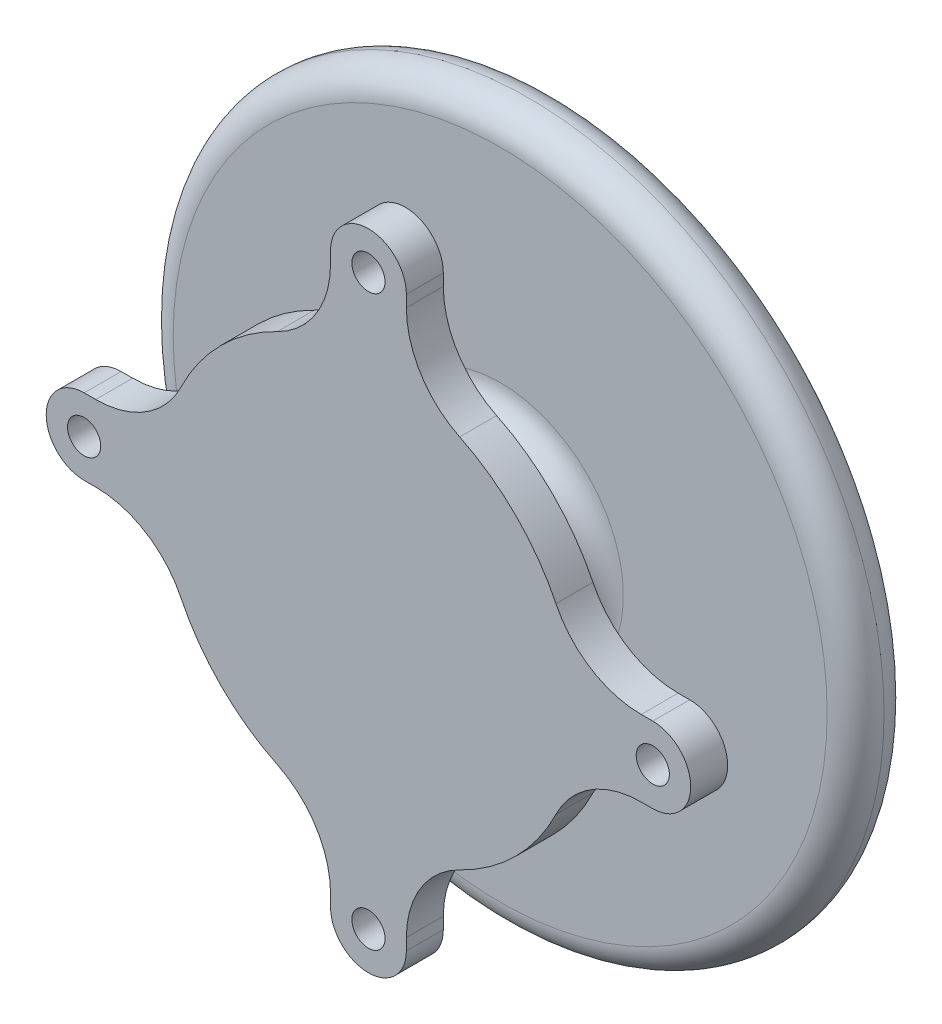
SolidWorks part; units mm, degrees
ref_plane "Front Plane" through (0, 0, 0) normal (0, 0, 1) x (1, 0, 0)
ref_plane "Top Plane" through (0, 0, 0) normal (0, 1, 0) x (1, 0, 0)
ref_plane "Right Plane" through (0, 0, 0) normal (1, 0, 0) x (0, 0, -1)
sketch "Sketch1" plane through (0, 0, 0) normal (0, 0, 1) x (1, 0, 0)
  circle A0 centre (0, 0) radius 25
  dimension "D1" = 50
ref_plane "Plane1" through (0, 0, 20) normal (0, 0, 1) x (1, 0, 0)
sketch "Sketch2" plane through (0, 0, 20) normal (0, 0, 1) x (1, 0, 0)
  circle A0 centre (0, 0) radius 15
  dimension "D1" = 30
loft "Loft1" add profiles "Sketch2", "Sketch1" connector at (-14.1852, 4.8766, 20) connector at (-23.533, 8.4378, 0)
sketch "Sketch3" plane through (0, 0, 20) normal (0, 0, 1) x (1, 0, 0)
  circle A0 centre (0, 0) radius 15
  circle A1 centre (0, 0) radius 15 construction
extrude "Boss-Extrude1" add sketch "Sketch3" along normal blind 5
fillet "Fillet1" radius 10 1 edges at (15, 0, 20)
sketch "Sketch4" plane through (0, 0, 0) normal (0, 0, -1) x (-1, 0, 0)
  line L0 (0, 20) -> (0, -20) construction
  line L1 (-20, 0) -> (20, 0) construction
  circle A0 centre (0, 0) radius 20 construction
  circle A1 centre (0, 20) radius 1.75
  circle A2 centre (-20, 0) radius 1.75
  circle A3 centre (0, -20) radius 1.75
  circle A4 centre (20, 0) radius 1.75
  dimension "D1" = 40
  dimension "D2" = 3.5
  dimension "D3" = 3.5
  dimension "D4" = 3.5
  dimension "D5" = 3.5
extrude "Cut-Extrude1" cut sketch "Sketch4" against normal blind 130
ref_plane "Plane2" through (0, 0, 3) normal (0, 0, -1) x (-1, 0, 0)
sketch "Sketch5" plane through (0, 0, 3) normal (0, 0, -1) x (-1, 0, 0)
  circle A0 centre (0, 20) radius 4
  circle A1 centre (20, 0) radius 4
  circle A3 centre (-20, 0) radius 4
  circle A5 centre (0, -20) radius 4
  dimension "D1" = 8
  dimension "D2" = 8
  dimension "D3" = 8
  dimension "D4" = 8
extrude "Cut-Extrude2" cut sketch "Sketch5" against normal blind 130
sketch "Sketch6" plane through (0, 0, 25) normal (0, 0, 1) x (1, 0, 0)
  circle A0 centre (0, 0) radius 22
  dimension "D1" = 44
extrude "Boss-Extrude2" add sketch "Sketch6" along normal blind 4
sketch "Sketch7" plane through (0, 0, 29) normal (0, 0, 1) x (1, 0, 0)
  circle A0 centre (0, 0) radius 17
  circle A1 centre (0, 0) radius 22 construction
  dimension "D1" = 5
extrude "Boss-Extrude3" add sketch "Sketch7" along normal blind 20
sketch "Sketch8" [suppressed] plane through (0, 0, 0) normal (0, 1, 0) x (1, 0, 0)
  line L0 (0, -48) -> (0, -27)
  line L1 (-17, -48) -> (17, -48) construction
  line L3 (17, -48) -> (17, -28) construction
  line L4 (3, -24) -> (45.4819, -24)
  arc A0 (0, -27) -> (3, -24) centre (3, -27) cw
  point P9 (0, -24)
  dimension "D2" = 3
  dimension "D1" = 24
  dimension "D3" = 17
ref_plane "Plane5" through (14, 0, 0) normal (1, 0, 0) x (0, 0, -1)
sketch "Sketch14" [suppressed] plane through (14, 0, 0) normal (1, 0, 0) x (0, 0, -1)
  line L0 (-28, 20) -> (-28, -20) construction
  circle A0 centre (-24, 0) radius 4
  dimension "D1" = 8
sketch "Sketch9" [suppressed] plane through (0, 0, 48) normal (0, 0, 1) x (1, 0, 0)
  circle A0 centre (0, 0) radius 2.1
  dimension "D1" = 4.2
ref_plane "Plane4" through (14, 0, 0) normal (1, 0, 0) x (0, 0, -1)
sketch "Sketch10" plane through (0, 0, 49) normal (0, 0, 1) x (1, 0, 0)
  circle A0 centre (0, 0) radius 10
  circle A1 centre (0, 0) radius 17 construction
  dimension "D1" = 7
sketch "Sketch13" [suppressed] plane through (0, 0, 0) normal (0, 1, 0) x (1, 0, 0)
  line L0 (17, -28) -> (17, -48) construction
  line L1 (-20, -28) -> (20, -28) construction
  line L2 (17, -31.3668) -> (17, -44.6332)
  line L3 (0, -28) -> (0, -48) construction
  line L4 (-17, -28) -> (17, -28) construction
  line L5 (-17, -48) -> (17, -48) construction
  arc A0 (17, -31.3668) -> (17, -44.6332) centre (38.5, -38) ccw
  dimension "D1" = 45
  dimension "D2" = 21.5
  dimension "D3" = 10
ref_plane "Plane14" through (0, 0, 39) normal (0, 0, 1) x (1, 0, 0)
sketch "Sketch15" plane through (0, 0, 0) normal (0, 1, 0) x (1, 0, 0)
  line L0 (-17, -29) -> (-17, -49) construction
  line L1 (-21.4316, -33) -> (-13, -33)
  line L2 (-21.4316, -33) -> (-21.4316, -37)
  line L3 (-21.4316, -37) -> (-13, -37)
  line L4 (-13, -33) -> (-13, -37)
  line L5 (-21.5787, -41) -> (-13, -41)
  line L6 (-21.5787, -41) -> (-21.5787, -45)
  line L7 (-21.5787, -45) -> (-13, -45)
  line L8 (-13, -41) -> (-13, -45)
  line L9 (-17, -29) -> (17, -29) construction
  line L10 (0, -29) -> (0, -49) construction
  line L11 (-17, -49) -> (17, -49) construction
  dimension "D1" = 4
  dimension "D2" = 4
  dimension "D3" = 4
  dimension "D4" = 4
  dimension "D5" = 4
  dimension "D6" = 4
revolve "Cut-Revolve1" cut sketch "Sketch15" angle 360 about L10
sketch "Sketch18" plane through (0, 0, 0) normal (0, 0, -1) x (-1, 0, 0)
  circle A0 centre (0, 0) radius 12.5
  dimension "D1" = 25
extrude "Cut-Extrude5" cut sketch "Sketch18" against normal blind 20
sketch "Sketch19" plane through (0, 0, 25) normal (0, 0, -1) x (-1, 0, 0)
  circle A0 centre (0, 0) radius 47.9872
extrude "Cut-Extrude6" cut sketch "Sketch19" along normal through all
sketch "Sketch20" plane through (0, 0, 25) normal (0, 0, -1) x (-1, 0, 0)
  line L0 (-4, 30) -> (-4, 21.6333)
  line L1 (4, 30) -> (4, 21.6333)
  arc A0 (4, 30) -> (-4, 30) centre (0, 30) ccw
  circle A1 centre (0, 30) radius 1.75
  arc A2 (4, 21.6333) -> (-4, 21.6333) centre (0, 0) ccw
  dimension "D1" = 8
  dimension "D2" = 3.5
  dimension "D3" = 44
  dimension "D4" = 30
extrude "Boss-Extrude5" add sketch "Sketch20" against normal blind 4
pattern_circular "CirPattern3" count 4 over 360 about axis through (0, 0, 25) along (0, 0, 1) of "Boss-Extrude5"
fillet "Fillet2" radius 10 8 edges at (21.6333, 4, 27) (21.6333, -4, 27) (4, -21.6333, 27) (-4, -21.6333, 27) (-21.6333, -4, 27) (-21.6333, 4, 27) (-4, 21.6333, 27) (4, 21.6333, 27)
sketch "Sketch21" plane through (0, 0, 29) normal (0, 0, 1) x (1, 0, 0)
  circle A0 centre (0, 0) radius 20
  circle A1 centre (0, 0) radius 17 construction
  circle A2 centre (0, 0) radius 26
  dimension "D1" = 3
  dimension "D2" = 6
chamfer "Chamfer1" distance 0.5 angle 45 5 edges at (-17, 0, 33) (-17, 0, 41) (17, 0, 37) (17, 0, 49) (17, 0, 45)
sketch "Sketch22" plane through (0, 0, 0) normal (0, 1, 0) x (1, 0, 0)
  line L0 (0, -49) -> (0, -60.7563) construction
  line L1 (7.5, -57) -> (-7.5, -57)
  line L2 (7.5, -57) -> (7.5, -49)
  line L3 (7.5, -49) -> (-7.5, -49)
  line L4 (-7.5, -57) -> (-7.5, -49)
  line L5 (-16.5, -49) -> (16.5, -49) construction
  dimension "D1" = 15
  dimension "D2" = 8
  dimension "D3" = 7.5
extrude "Boss-Extrude6" add sketch "Sketch22" along normal mid plane 15
sketch "Sketch23" plane through (0, 0, 0) normal (0, 1, 0) x (1, 0, 0)
  line L0 (0, -57) -> (0, -66) construction
  line L1 (-7.5, -57) -> (7.5, -57) construction
  line L2 (7.5, -57) -> (7.5, -49) construction
  line L3 (7.5, -53.0096) -> (7.5, -49)
  line L4 (-7.5, -49) -> (-7.5, -57) construction
  line L5 (-7.5, -49) -> (-7.5, -53.0096)
  line L6 (-7.5, -49) -> (7.5, -49)
  arc A0 (7.5, -53.0096) -> (-7.5, -53.0096) centre (0, -66) ccw
  dimension "D2" = 30
  dimension "D1" = 9
extrude "Cut-Extrude7" cut sketch "Sketch23" against normal mid plane 1.5
chamfer "Chamfer2" distance 3 angle 45 4 edges at (7.5, -7.5, 53) (7.5, 7.5, 53) (-7.5, -7.5, 53) (-7.5, 7.5, 53)
chamfer "Chamfer3" distance 0.5 angle 45 18 edges at (-6, -6, 57) (-7.5, 0, 57) (-6, 6, 57) (0, 7.5, 57) (6, 6, 57) (7.5, 0, 57) (6, -6, 57) (0, -7.5, 57) (7.5, 2.625, 49) (6, 6, 49) (0, 7.5, 49) (-6, 6, 49) (-7.5, 2.625, 49) (7.5, -2.625, 49) (6, -6, 49) (-7.5, -2.625, 49) (-6, -6, 49) (0, -7.5, 49)
sketch "Sketch24" plane through (0, 0, 29) normal (0, 0, 1) x (1, 0, 0)
  circle A0 centre (0, 0) radius 41.0173
  circle A1 centre (0, 0) radius 17 construction
  circle A2 centre (0, 0) radius 17
extrude "Cut-Extrude8" cut sketch "Sketch24" against normal blind 0.1
sketch "Sketch25" plane through (0, 0, 25) normal (0, 0, -1) x (-1, 0, 0)
  line L8 (4, 28.775) -> (4, 30)
  line L9 (-4, 30) -> (-4, 28.775)
  line L10 (-28.775, 4) -> (-30, 4)
  line L11 (-30, -4) -> (-28.775, -4)
  line L12 (-4, -28.775) -> (-4, -30)
  line L13 (4, -30) -> (4, -28.775)
  line L14 (28.775, -4) -> (30, -4)
  line L15 (30, 4) -> (28.775, 4)
  line L16 (4, 28.775) -> (4, 30)
  line L17 (-4, 30) -> (-4, 28.775)
  line L18 (-28.775, 4) -> (-30, 4)
  line L19 (-30, -4) -> (-28.775, -4)
  line L20 (-4, -28.775) -> (-4, -30)
  line L21 (4, -30) -> (4, -28.775)
  line L22 (28.775, -4) -> (30, -4)
  line L23 (30, 4) -> (28.775, 4)
  circle A0 centre (30, 0) radius 1.75 construction
  circle A1 centre (0, 30) radius 1.75 construction
  circle A2 centre (-30, 0) radius 1.75 construction
  circle A3 centre (0, -30) radius 1.75 construction
  circle A4 centre (30, 0) radius 1.75
  circle A5 centre (0, 30) radius 1.75
  circle A6 centre (-30, 0) radius 1.75
  circle A7 centre (0, -30) radius 1.75
  arc A16 (19.7828, 9.625) -> (9.625, 19.7828) centre (0, 0) ccw
  arc A17 (4, 28.775) -> (9.625, 19.7828) centre (14, 28.775) ccw
  arc A18 (4, 30) -> (-4, 30) centre (0, 30) ccw
  arc A19 (-9.625, 19.7828) -> (-4, 28.775) centre (-14, 28.775) ccw
  arc A20 (-9.625, 19.7828) -> (-19.7828, 9.625) centre (0, 0) ccw
  arc A21 (-28.775, 4) -> (-19.7828, 9.625) centre (-28.775, 14) ccw
  arc A22 (-30, 4) -> (-30, -4) centre (-30, 0) ccw
  arc A23 (-19.7828, -9.625) -> (-28.775, -4) centre (-28.775, -14) ccw
  arc A24 (-19.7828, -9.625) -> (-9.625, -19.7828) centre (0, 0) ccw
  arc A25 (-4, -28.775) -> (-9.625, -19.7828) centre (-14, -28.775) ccw
  arc A26 (-4, -30) -> (4, -30) centre (0, -30) ccw
  arc A27 (9.625, -19.7828) -> (4, -28.775) centre (14, -28.775) ccw
  arc A28 (9.625, -19.7828) -> (19.7828, -9.625) centre (0, 0) ccw
  arc A29 (28.775, -4) -> (19.7828, -9.625) centre (28.775, -14) ccw
  arc A30 (30, -4) -> (30, 4) centre (30, 0) ccw
  arc A31 (19.7828, 9.625) -> (28.775, 4) centre (28.775, 14) ccw
  arc A32 (19.7828, 9.625) -> (9.625, 19.7828) centre (0, 0) ccw
  arc A33 (4, 28.775) -> (9.625, 19.7828) centre (14, 28.775) ccw
  arc A34 (4, 30) -> (-4, 30) centre (0, 30) ccw
  arc A35 (-9.625, 19.7828) -> (-4, 28.775) centre (-14, 28.775) ccw
  arc A36 (-9.625, 19.7828) -> (-19.7828, 9.625) centre (0, 0) ccw
  arc A37 (-28.775, 4) -> (-19.7828, 9.625) centre (-28.775, 14) ccw
  arc A38 (-30, 4) -> (-30, -4) centre (-30, 0) ccw
  arc A39 (-19.7828, -9.625) -> (-28.775, -4) centre (-28.775, -14) ccw
  arc A40 (-19.7828, -9.625) -> (-9.625, -19.7828) centre (0, 0) ccw
  arc A41 (-4, -28.775) -> (-9.625, -19.7828) centre (-14, -28.775) ccw
  arc A42 (-4, -30) -> (4, -30) centre (0, -30) ccw
  arc A43 (9.625, -19.7828) -> (4, -28.775) centre (14, -28.775) ccw
  arc A44 (9.625, -19.7828) -> (19.7828, -9.625) centre (0, 0) ccw
  arc A45 (28.775, -4) -> (19.7828, -9.625) centre (28.775, -14) ccw
  arc A46 (30, -4) -> (30, 4) centre (30, 0) ccw
  arc A47 (19.7828, 9.625) -> (28.775, 4) centre (28.775, 14) ccw
  dimension "D1" = 0
sketch "Sketch26" plane through (0, 0, 0) normal (0, 1, 0) x (1, 0, 0)
  line L0 (19.7828, -28.9) -> (28.775, -28.9) construction
  line L1 (-41.2328, -64.4564) -> (45.017, -64.4564)
  line L2 (-41.2328, -64.4564) -> (-41.2328, -28.9)
  line L3 (-41.2328, -28.9) -> (45.017, -28.9)
  line L4 (45.017, -64.4564) -> (45.017, -28.9)
extrude "Cut-Extrude9" cut sketch "Sketch26" against normal mid plane 100
sketch "Sketch27" plane through (0, 0, 25) normal (0, 0, -1) x (-1, 0, 0)
  circle A0 centre (0, 0) radius 10
  dimension "D1" = 20
extrude "Boss-Extrude7" add sketch "Sketch27" along normal blind 10 contours A0
sketch "Sketch28" plane through (0, 0, 15) normal (0, 0, -1) x (-1, 0, 0)
  circle A0 centre (0, 0) radius 37.5
  dimension "D1" = 75
extrude "Boss-Extrude8" add sketch "Sketch28" along normal blind 6
fillet "Fillet3" radius 3 4 edges at (-10, 0, 15) (-10, 0, 25) (-37.5, 0, 15) (-37.5, 0, 9)
